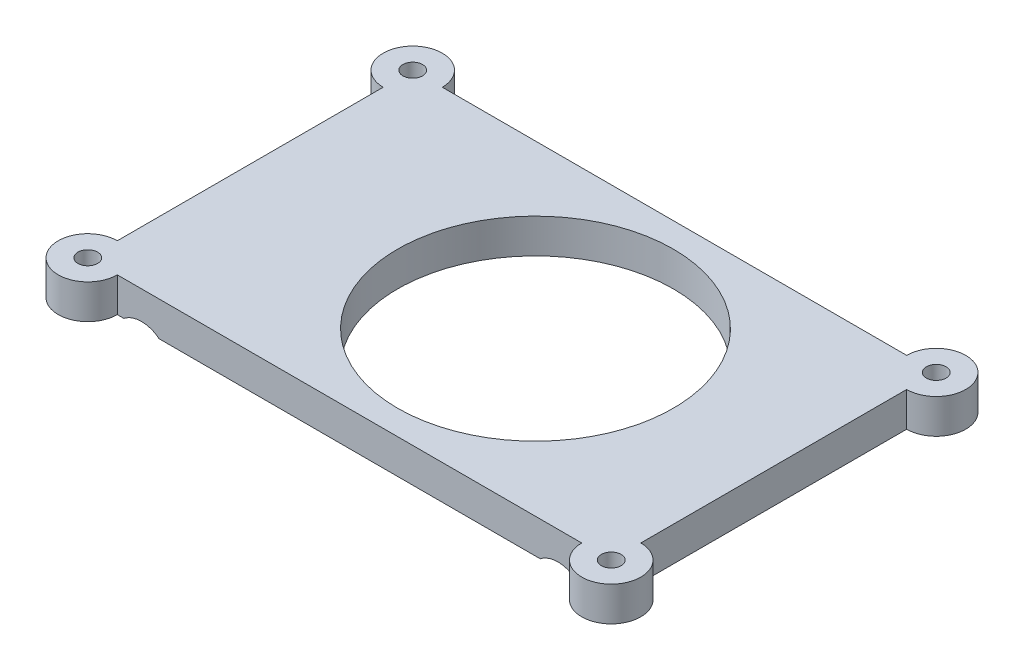
SolidWorks part; units mm, degrees
ref_plane "前视" through (0, 0, 0) normal (0, 0, 1) x (1, 0, 0)
ref_plane "上视" through (0, 0, 0) normal (0, 1, 0) x (1, 0, 0)
ref_plane "右视" through (0, 0, 0) normal (1, 0, 0) x (0, 0, -1)
sketch "Sketch1" plane through (0, 0, 0) normal (0, 1, 0) x (1, 0, 0)
  line L0 (53.16, -33) -> (-53.16, -33)
  line L1 (53.16, -33) -> (53.16, 33)
  line L2 (-53.16, -33) -> (-53.16, 33)
  line L3 (53.16, 33) -> (-53.16, 33)
  line L4 (53.16, -33) -> (-53.16, 33) construction
  line L5 (-53.16, -33) -> (53.16, 33) construction
  line L6 (-31.4, 33) -> (-31.4, -33)
  line L7 (31.4, 33) -> (31.4, -33)
  point P1 (0, 0)
  dimension "D1" = 106.32
  dimension "D2" = 66
  dimension "D3" = 21.76
  dimension "D4" = 21.76
extrude "Boss-Extrude1" add sketch "Sketch1" along normal blind 10 contours L6 L3 L2 L0 | L7 L3 L6 L0 | L3 L7 L0 L1 region at (42.28, 0, 0) region at (0, 0, 0) region at (-42.28, 0, 0)
extrude "Cut-Extrude1" cut sketch "Sketch1<5>" along normal blind 5 contours L7 L3 L6 L0 region at (0, 0, 0)
sketch "Sketch1<5>" plane through (0, 0, 0) normal (0, 1, 0) x (1, 0, 0) same geometry as "Sketch1"
ref_plane "Plane1" through (0, 0, 31) normal (0, 0, 1) x (1, 0, 0)
sketch "Sketch3" plane through (0, 0, 31) normal (0, 0, 1) x (1, 0, 0)
  line L0 (-53.16, 10) -> (-53.16, 0) construction
  line L1 (-31.4, 0) -> (-53.16, 0) construction
  line L2 (53.16, 10) -> (53.16, 0) construction
  line L3 (53.16, 0) -> (31.4, 0) construction
  circle A0 centre (-42.25, -4.5) radius 7.65
  circle A1 centre (42.31, -4.5) radius 7.65
  circle A2 centre (42.31, -4.5) radius 5.75
  circle A3 centre (-42.25, -4.5) radius 5.75
  point P0 (-42.25, -4.5)
  point P7 (42.31, -4.5)
  dimension "D3" = 10.85
  dimension "D1" = 10.91
  dimension "D2" = 4.5
  dimension "D4" = 4.5
extrude "Cut-Extrude2" cut sketch "Sketch3" against normal offset from surface (62 mm away) 2 contours A3 | A0 A3 | A2 | A1 A2 region at (-49.6836, -4.5, 31) region at (34.8764, -4.5, 31) region at (42.31, -4.5, 31) region at (-42.25, -4.5, 31) up to face at (0, 3.75, -33)
extrude "Cut-Extrude3" cut sketch "Sketch3<3>" against normal through all both and the other way through all contours A2 | A3 region at (42.31, -4.5, 31) region at (-42.25, -4.5, 31)
sketch "Sketch3<3>" plane through (0, 0, 31) normal (0, 0, 1) x (1, 0, 0) same geometry as "Sketch3"
sketch "Sketch4" plane through (0, 0, 0) normal (0, -1, 0) x (1, 0, 0)
  line L0 (-47.16, 33) -> (-53.16, 33)
  line L1 (-53.16, 33) -> (-53.16, 27)
  line L2 (-47.16, -33) -> (-53.16, -33)
  line L3 (-53.16, -33) -> (-53.16, -27)
  line L4 (53.16, -27) -> (53.16, -33)
  line L5 (53.16, -33) -> (47.16, -33)
  line L6 (47.16, 33) -> (53.16, 33)
  line L7 (53.16, 33) -> (53.16, 27)
  circle A0 centre (53.16, 33) radius 6
  circle A1 centre (53.16, -33) radius 6
  circle A2 centre (-53.16, -33) radius 6
  circle A3 centre (-53.16, 33) radius 6
  circle A4 centre (53.16, 33) radius 2
  circle A5 centre (53.16, -33) radius 2
  circle A6 centre (-53.16, -33) radius 2
  circle A7 centre (-53.16, 33) radius 2
  line M1 (53.16, 33) -> (45.8895, 33)
  line M7 (45.8895, -33) -> (53.16, -33)
  line M8 (53.16, -33) -> (53.16, 33)
extrude "Boss-Extrude2" add sketch "Sketch4" against normal up to surface (10 mm away) contours A4 A0 L6 M8 | A5 A1 L4 M7 | A7 L0 A3 L1 | A6 L3 A2 L2 region at (-49.16, 0, 33.1697) region at (-57.2826, 0, -37.1226) region at (57.2826, 0, -28.8774) region at (53.3297, 0, 29) up to face at (0, 10, 0)
extrude "Cut-Extrude4" cut sketch "Sketch4<3>" against normal through all contours A4 L7 M1 | A5 L5 M8 | L2 A6 L3 | L1 A7 L0 region at (-52.3112, 0, 32.1512) region at (-52.3112, 0, -32.1512) region at (52.3112, 0, -32.1512) region at (52.3112, 0, 32.1512)
sketch "Sketch4<3>" plane through (0, 0, 0) normal (0, -1, 0) x (1, 0, 0) same geometry as "Sketch4"
sketch "Sketch5" plane through (0, 10, 0) normal (0, 1, 0) x (1, 0, 0)
  line L2 (53.16, -27) -> (53.16, 27) construction
  line L3 (31.4, 33) -> (-31.4, 33) construction
  line L4 (19.1575, -33) -> (-9.6175, -33)
  line L5 (47.16, -33) -> (-47.16, -33) construction
  line L6 (-9.6175, 33) -> (19.1575, 33)
  line L7 (47.16, 33) -> (-47.16, 33) construction
  circle A0 centre (4.77, 0) radius 28
  circle A1 centre (4.77, 0) radius 36
  point P0 (4.77, 0)
  dimension "D3" = 56
  dimension "D1" = 48.39
  dimension "D2" = 33
extrude "Cut-Extrude5" cut sketch "Sketch5" against normal through all contours A0 region at (4.77, 10, 0)
sketch "Sketch6" plane through (0, 5, 0) normal (0, -1, 0) x (1, 0, 0)
  line L5 (31.4, -33) -> (31.4, -8.6512)
  line L6 (31.4, 8.6512) -> (31.4, 33)
  line L7 (31.4, 33) -> (-31.4, 33)
  line L8 (-31.4, 33) -> (-31.4, -33)
  line L9 (-31.4, -33) -> (31.4, -33)
  line L10 (31.4, -33) -> (31.4, -8.6512)
  line L11 (31.4, 8.6512) -> (31.4, 33)
  line L12 (31.4, 33) -> (-31.4, 33)
  line L13 (-31.4, 33) -> (-31.4, -33)
  line L14 (-31.4, -33) -> (31.4, -33)
  arc A1 (31.4, 8.6512) -> (31.4, -8.6512) centre (4.77, 0) ccw
  arc A2 (31.4, 8.6512) -> (31.4, -8.6512) centre (4.77, 0) ccw
  dimension "D1" = 0
extrude "Boss-Extrude3" add sketch "Sketch6" along normal up to surface (5 mm away) up to face at (49.5676, 0, 0)
sketch "Sketch8" plane through (0, 10, 0) normal (0, 1, 0) x (1, 0, 0)
  line L4 (-53.16, 27) -> (-53.16, -27)
  line L5 (-47.16, -33) -> (47.16, -33)
  line L6 (53.16, -27) -> (53.16, 27)
  line L7 (47.16, 33) -> (-47.16, 33)
  line L8 (-53.16, 27) -> (-53.16, -27)
  line L9 (-47.16, -33) -> (47.16, -33)
  line L10 (53.16, -27) -> (53.16, 27)
  line L11 (47.16, 33) -> (-47.16, 33)
  arc A4 (-47.16, 33) -> (-53.16, 27) centre (-53.16, 33) ccw
  arc A5 (-53.16, -27) -> (-47.16, -33) centre (-53.16, -33) ccw
  arc A6 (47.16, -33) -> (53.16, -27) centre (53.16, -33) ccw
  arc A7 (53.16, 27) -> (47.16, 33) centre (53.16, 33) ccw
  arc A8 (-47.16, 33) -> (-53.16, 27) centre (-53.16, 33) ccw
  arc A9 (-53.16, -27) -> (-47.16, -33) centre (-53.16, -33) ccw
  arc A10 (47.16, -33) -> (53.16, -27) centre (53.16, -33) ccw
  arc A11 (53.16, 27) -> (47.16, 33) centre (53.16, 33) ccw
  dimension "D1" = 0
extrude "Cut-Extrude6" cut sketch "Sketch8" against normal blind 3
